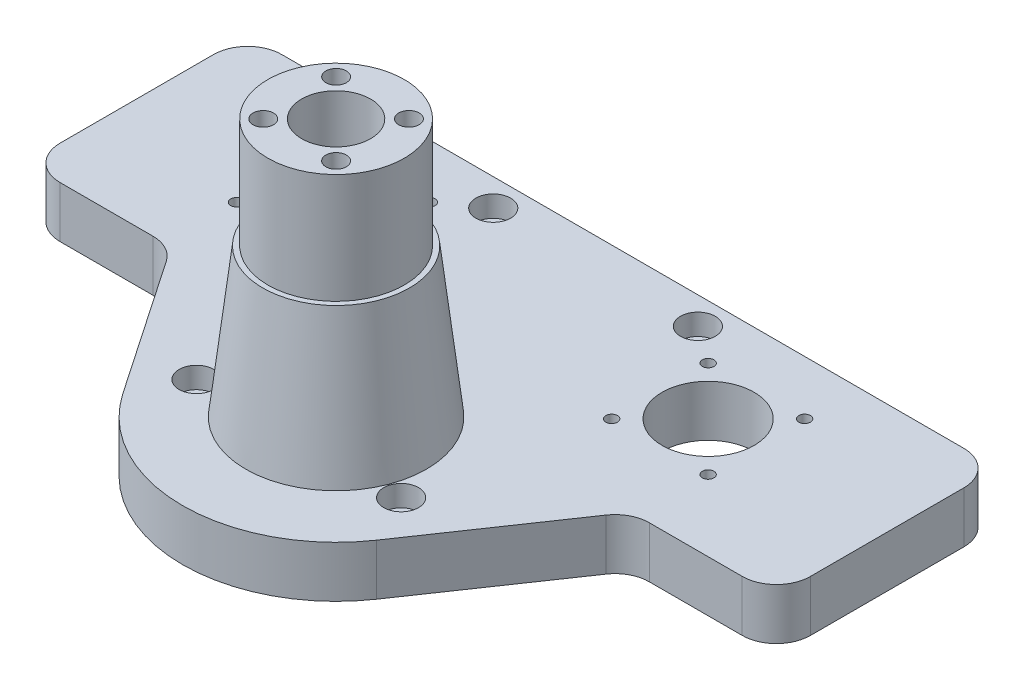
SolidWorks part; units mm, degrees
material "PLA Infill"
ref_plane "Front Plane" through (0, 0, 0) normal (0, 0, 1) x (1, 0, 0)
ref_plane "Top Plane" through (0, 0, 0) normal (0, 1, 0) x (1, 0, 0)
ref_plane "Right Plane" through (0, 0, 0) normal (1, 0, 0) x (0, 0, -1)
sketch "Sketch1" plane through (0, 0, 0) normal (0, 1, 0) x (1, 0, 0)
  line L0 (0, 0) -> (55, 54.0672) construction
  line L1 (55, 54.0672) -> (-55, 54.0672) construction
  line L2 (-55, 54.0672) -> (0, 0) construction
  line L3 (-79.7903, 37.1722) -> (-37.1854, -25.3425) construction
  line L4 (-55, 84.0672) -> (55, 84.0672)
  line L5 (37.1854, -25.3425) -> (79.7903, 37.1722) construction
  line L6 (-55, 84.0672) -> (-100, 84.0672)
  line L7 (-110, 74.0672) -> (-110, 29.0672)
  line L8 (-100, 19.0672) -> (-72.7378, 19.0672)
  line L9 (-64.4743, 14.6989) -> (-37.1854, -25.3425)
  line L10 (0, -1000) -> (0, 49000) construction
  line L11 (64.4743, 14.6989) -> (37.1854, -25.3425)
  line L12 (100, 19.0672) -> (72.7378, 19.0672)
  line L13 (110, 74.0672) -> (110, 29.0672)
  line L14 (55, 84.0672) -> (100, 84.0672)
  circle A0 centre (-55, 54.0672) radius 30 construction
  circle A1 centre (55, 54.0672) radius 30 construction
  circle A2 centre (0, 0) radius 45 construction
  arc A3 (-79.7903, 37.1722) -> (-55, 84.0672) centre (-55, 54.0672) cw construction
  arc A4 (55, 84.0672) -> (79.7903, 37.1722) centre (55, 54.0672) cw construction
  arc A5 (-37.1854, -25.3425) -> (37.1854, -25.3425) centre (0, 0) ccw
  arc A6 (-72.7378, 19.0672) -> (-64.4743, 14.6989) centre (-72.7378, 9.0672) cw
  arc A7 (-110, 29.0672) -> (-100, 19.0672) centre (-100, 29.0672) ccw
  arc A8 (-100, 84.0672) -> (-110, 74.0672) centre (-100, 74.0672) ccw
  arc A9 (72.7378, 19.0672) -> (64.4743, 14.6989) centre (72.7378, 9.0672) ccw
  arc A10 (110, 29.0672) -> (100, 19.0672) centre (100, 29.0672) cw
  arc A11 (100, 84.0672) -> (110, 74.0672) centre (100, 74.0672) cw
  point P23 (-67.4514, 19.0672)
  dimension "D3" = 60
  dimension "D4" = 90
  dimension "D5" = 10
  dimension "D6" = 55
  dimension "D1" = 110
  dimension "D2" = 77.125
  dimension "D7" = 35
extrude "Main Body" add sketch "Sketch1" along normal blind 15 contours A5 L11 A9 L12 A10 L13 A11 L14 L4 L6 A8 L7 A7 L8 A6 L9
sketch "Sketch3" plane through (0, 15, 0) normal (0, 1, 0) x (1, 0, 0)
  circle A0 centre (0, 0) radius 45 construction
  circle A1 centre (0, 0) radius 45 construction
  circle A2 centre (0, 0) radius 21.5
  dimension "D1" = 43
extrude "Front Extrusion" add sketch "Sketch3" along normal blind 75.7
ref_plane "First Bearing Section" through (0, 58.5, 0) normal (0, 1, 0) x (1, 0, 0)
sketch "Front Loft" plane through (0, 58.5, 0) normal (0, 1, 0) x (1, 0, 0)
  circle A0 centre (0, 0) radius 21.5
  dimension "D1" = 43
sketch "Back Loft" plane through (0, 15, 0) normal (0, 1, 0) x (1, 0, 0)
  circle A0 centre (0, 0) radius 26.5
  dimension "D1" = 53
loft "Lofted Taper" add profiles "Front Loft", "Back Loft" connector at (0, 58.5, 21.5) connector at (0, 15, 26.5)
sketch "Sketch4" plane through (0, 0, 0) normal (0, -1, 0) x (1, 0, 0)
  line L0 (0, -1000) -> (0, 49000) construction
  line L1 (-45, 0) -> (45, 0) construction
  line L2 (-85, -54.0672) -> (-25, -54.0672) construction
  line L3 (55, -54.0672) -> (-55, -54.0672) construction
  line L4 (-55, -24.0672) -> (-55, -84.0672) construction
  line L5 (-10.6773, 10.6773) -> (0, 0) construction
  line L6 (-10.6773, -10.6773) -> (0, 0) construction
  line L7 (-69.1421, -39.9251) -> (-55, -54.0672) construction
  line L8 (-100, -84.0672) -> (100, -84.0672) construction
  line L9 (100, -84.0672) -> (-100, -84.0672) construction
  line L10 (-30, -76.0672) -> (0, -76.0672) construction
  line L11 (-30, -76.0672) -> (-30, 10.9328) construction
  line L12 (-30, 10.9328) -> (0, 10.9328) construction
  line L13 (0, -76.0672) -> (0, 10.9328) construction
  circle A0 centre (55, -54.0672) radius 30 construction
  circle A1 centre (0, 0) radius 45 construction
  circle A2 centre (-55, -54.0672) radius 30 construction
  circle A3 centre (55, -54.0672) radius 30 construction
  circle A4 centre (0, 0) radius 45 construction
  circle A5 centre (-55, -54.0672) radius 30 construction
  circle A6 centre (0, 0) radius 10.1
  circle A7 centre (-55, -54.0672) radius 13.5
  circle A10 centre (-10.6773, 10.6773) radius 3
  circle A13 centre (-10.6773, -10.6773) radius 3
  circle A14 centre (-69.1421, -39.9251) radius 1.7
  circle A15 centre (-69.1421, -68.2094) radius 1.7
  circle A16 centre (-40.8579, -68.2094) radius 1.7
  circle A17 centre (-40.8579, -39.9251) radius 1.7
  circle A18 centre (55, -54.0672) radius 13.5
  circle A19 centre (69.1421, -68.2094) radius 1.7
  circle A20 centre (40.8579, -68.2094) radius 1.7
  circle A21 centre (40.8579, -39.9251) radius 1.7
  circle A22 centre (69.1421, -39.9251) radius 1.7
  circle A23 centre (10.6773, -10.6773) radius 3
  circle A24 centre (10.6773, 10.6773) radius 3
  circle A25 centre (-30, -76.0672) radius 3
  circle A26 centre (-30, 10.9328) radius 3
  circle A27 centre (30, -76.0672) radius 3
  circle A28 centre (30, 10.9328) radius 3
  dimension "D1" = 20.2
  dimension "D2" = 27
  dimension "D4" = 6
  dimension "D5" = 45
  dimension "D7" = 3.4
  dimension "D9" = 6
  dimension "D3" = 15.1
  dimension "D6" = 20
  dimension "D8" = 45
  dimension "D10" = 30
  dimension "D11" = 8
  dimension "D12" = 87
extrude "Bolt Holes" cut sketch "Sketch4" against normal through all
sketch "Sketch5" plane through (0, 0, 0) normal (0, -1, 0) x (1, 0, 0)
  line L0 (-14.2836, 7.0711) -> (-9.7707, 2.5582)
  line L1 (-7.0711, 14.2836) -> (-2.5582, 9.7707)
  line L2 (-10.6773, 10.6773) -> (0, 0) construction
  line L3 (-1000, 0) -> (49000, 0) construction
  line L4 (0, -1000) -> (0, 49000) construction
  line L5 (-14.2836, -7.0711) -> (-9.7707, -2.5582)
  line L6 (-7.0711, -14.2836) -> (-2.5582, -9.7707)
  line L7 (7.0711, -14.2836) -> (2.5582, -9.7707)
  line L8 (14.2836, -7.0711) -> (9.7707, -2.5582)
  line L9 (14.2836, 7.0711) -> (9.7707, 2.5582)
  line L10 (7.0711, 14.2836) -> (2.5582, 9.7707)
  circle A0 centre (-10.6773, 10.6773) radius 2 construction
  circle A1 centre (-10.6773, 10.6773) radius 5.1 construction
  circle A2 centre (0, 0) radius 10.1 construction
  arc A3 (-14.2836, 7.0711) -> (-7.0711, 14.2836) centre (-10.6773, 10.6773) cw
  circle A4 centre (0, 0) radius 10.1 construction
  arc A5 (-9.7707, 2.5582) -> (-2.5582, 9.7707) centre (0, 0) cw
  arc A6 (-14.2836, -7.0711) -> (-7.0711, -14.2836) centre (-10.6773, -10.6773) ccw
  arc A7 (-9.7707, -2.5582) -> (-2.5582, -9.7707) centre (0, 0) ccw
  arc A8 (14.2836, -7.0711) -> (7.0711, -14.2836) centre (10.6773, -10.6773) cw
  arc A9 (9.7707, -2.5582) -> (2.5582, -9.7707) centre (0, 0) cw
  arc A10 (14.2836, 7.0711) -> (7.0711, 14.2836) centre (10.6773, 10.6773) ccw
  arc A11 (9.7707, 2.5582) -> (2.5582, 9.7707) centre (0, 0) ccw
  dimension "D1" = 4
  dimension "D2" = 10.2
extrude "Bolt Recesses Rear" cut sketch "Sketch5" against normal blind 10
sketch "Sketch6" plane through (0, 15, 0) normal (0, 1, 0) x (1, 0, 0)
  circle A1 centre (30, 76.0672) radius 5.1
  circle A2 centre (-30, -10.9328) radius 3 construction
  circle A3 centre (30, -10.9328) radius 3 construction
  circle A4 centre (30, 76.0672) radius 3 construction
  circle A5 centre (-30, 76.0672) radius 3 construction
  circle A6 centre (-30, -10.9328) radius 3 construction
  circle A7 centre (30, -10.9328) radius 3 construction
  circle A8 centre (30, 76.0672) radius 3 construction
  circle A9 centre (-30, 76.0672) radius 3 construction
  circle A10 centre (-30, 76.0672) radius 5.1
  circle A11 centre (-30, -10.9328) radius 5.1
  circle A12 centre (30, -10.9328) radius 5.1
  dimension "D1" = 10.2
extrude "Bolt Recesses Front" cut sketch "Sketch6" against normal blind 6.2
sketch "Sketch7" plane through (0, 90.7, 0) normal (0, 1, 0) x (1, 0, 0)
  circle A0 centre (0, 0) radius 21.5 construction
  circle A1 centre (0, 0) radius 21.5
  circle A2 centre (0, 0) radius 20
  dimension "D1" = 40
extrude "Cut-Extrude1" cut sketch "Sketch7" against normal up to surface (32.2 mm away) up to plane "First Bearing Section"
sketch "Sketch8" plane through (0, 0, 0) normal (0, -1, 0) x (1, 0, 0)
  line L0 (0, -1000) -> (0, 49000) construction
  circle A0 centre (-69.1421, -68.2094) radius 1.7 construction
  circle A1 centre (-40.8579, -68.2094) radius 1.7 construction
  circle A2 centre (-40.8579, -39.9251) radius 1.7 construction
  circle A3 centre (-69.1421, -39.9251) radius 1.7 construction
  circle A4 centre (-69.1421, -68.2094) radius 1.7 construction
  circle A5 centre (-40.8579, -68.2094) radius 1.7 construction
  circle A6 centre (-40.8579, -39.9251) radius 1.7 construction
  circle A7 centre (-69.1421, -39.9251) radius 1.7 construction
  circle A8 centre (-69.1421, -39.9251) radius 2.85
  circle A9 centre (-40.8579, -39.9251) radius 2.85
  circle A10 centre (-40.8579, -68.2094) radius 2.85
  circle A11 centre (-69.1421, -68.2094) radius 2.85
  circle A12 centre (40.8579, -68.2094) radius 2.85
  circle A13 centre (40.8579, -39.9251) radius 2.85
  circle A14 centre (69.1421, -68.2094) radius 2.85
  circle A15 centre (69.1421, -39.9251) radius 2.85
  dimension "D1" = 5.7
extrude "Motor bolt head recesses" cut sketch "Sketch8" against normal blind 6
sketch "Sketch9" plane through (0, 0, 0) normal (0, -1, 0) x (1, 0, 0)
  line L0 (0, -1000) -> (0, 49000) construction
  line L1 (-110, -74.0672) -> (-110, -29.0672) construction
  line L2 (100, -84.0672) -> (-100, -84.0672) construction
  line L4 (-106, -74.0672) -> (-44, -74.0672) construction
  line L5 (-106, -74.0672) -> (-106, -32.0672) construction
  line L6 (-106, -32.0672) -> (-44, -32.0672) construction
  line L7 (-44, -74.0672) -> (-44, -32.0672) construction
  circle A0 centre (-106, -74.0672) radius 2
  circle A1 centre (-106, -32.0672) radius 2
  circle A2 centre (-44, -32.0672) radius 2
  circle A3 centre (-44, -74.0672) radius 2
  circle A4 centre (44, -74.0672) radius 2
  circle A5 centre (106, -74.0672) radius 2
  circle A6 centre (44, -32.0672) radius 2
  circle A7 centre (106, -32.0672) radius 2
  dimension "D3" = 4
  dimension "D1" = 4
  dimension "D2" = 10
  dimension "D4" = 62
  dimension "D5" = 42
extrude "Heat-set insert holes" cut sketch "Sketch9" against normal blind 6
sketch "Sketch10" plane through (0, 0, 0) normal (0, -1, 0) x (1, 0, 0)
  line L0 (0, -1000) -> (0, 49000) construction
  line L1 (-110, -74.0672) -> (-110, -29.0672) construction
  line L2 (100, -84.0672) -> (-100, -84.0672) construction
  line L4 (-95, -72.0672) -> (-55, -72.0672) construction
  line L5 (-95, -72.0672) -> (-95, -34.0672) construction
  line L6 (-95, -34.0672) -> (-55, -34.0672) construction
  line L7 (-55, -72.0672) -> (-55, -34.0672) construction
  circle A0 centre (-95, -72.0672) radius 1.6
  circle A1 centre (-95, -34.0672) radius 1.6
  circle A2 centre (-55, -34.0672) radius 1.6
  circle A3 centre (-55, -72.0672) radius 1.6
  circle A4 centre (95, -72.0672) radius 1.6
  circle A5 centre (55, -72.0672) radius 1.6
  circle A6 centre (55, -34.0672) radius 1.6
  circle A7 centre (95, -34.0672) radius 1.6
  dimension "D1" = 3.2
  dimension "D2" = 15
  dimension "D3" = 12
  dimension "D4" = 40
  dimension "D5" = 38
extrude "PCB Heat-set insert holes" cut sketch "Sketch10" against normal blind 4
